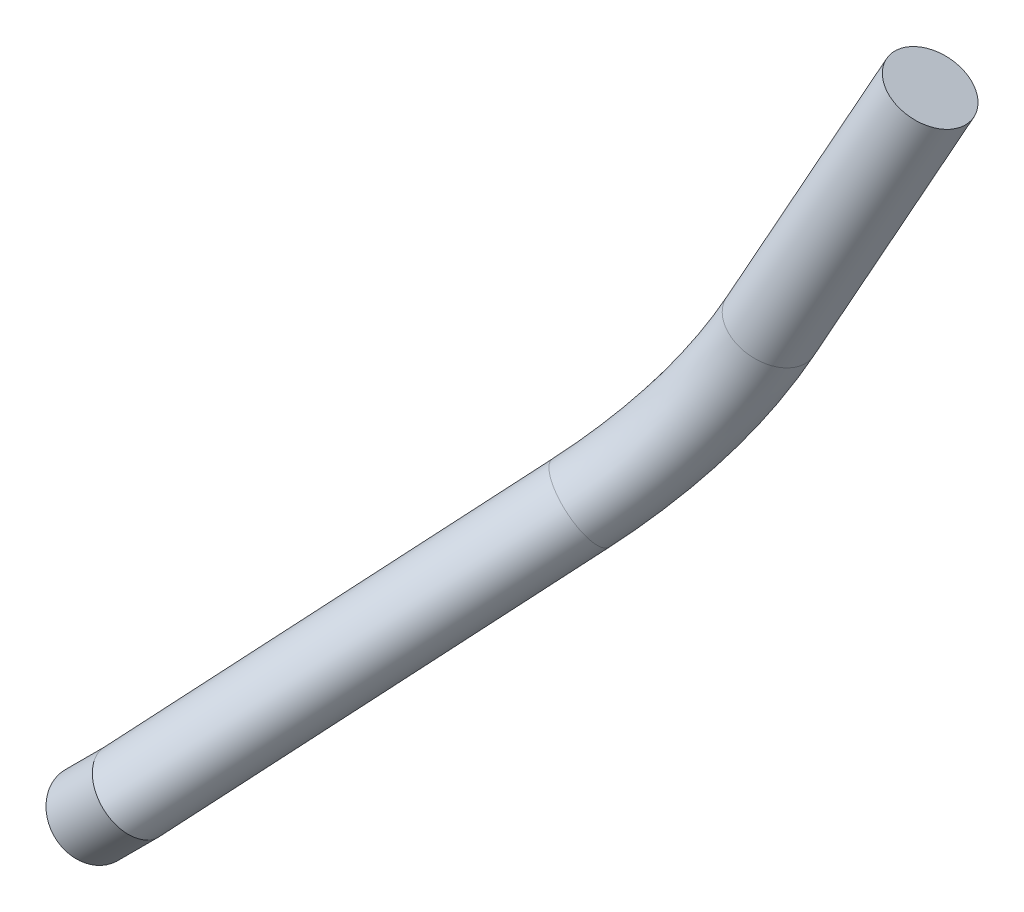
SolidWorks part; units mm, degrees
material "Custom Plastic"
ref_plane "X-Y Datum" through (0, 0, 0) normal (0, 0, 1) x (1, 0, 0)
ref_plane "X-Z Datum" through (0, 0, 0) normal (0, 1, 0) x (1, 0, 0)
ref_plane "Y-Z Datum" through (0, 0, 0) normal (1, 0, 0) x (0, 0, -1)
sketch3d "3DSketch1"
  line L0 (238.7544, 134.2697, 168.7024) -> (253.6203, 165.14, 163.3218)
  line L1 (198.0851, 82.9911, 208.7608) -> (193.0109, 77.9169, 208.7608)
  line L2 (198.0851, 82.9911, 208.7608) -> (225.2152, 113.3685, 179.1128)
  circle A0 centre (198.0851, 82.9911, 208.7608) radius 2.5146 construction
  arc A1 (253.6579, 165.1264, 159.3218) -> (253.6579, 165.1264, 167.3218) centre (253.6579, 165.1264, 163.3218) ccw construction
  arc A2 (253.6203, 165.14, 168.0218) -> (253.6203, 165.14, 158.6218) centre (253.6203, 165.14, 163.3218) ccw construction
  arc A3 (225.2152, 113.3685, 179.1128) -> (238.7544, 134.2697, 168.7024) centre (221.8528, 150.2787, 213.8543) ccw
  point P0 (198.0851, 82.9911, 208.7608)
  point P1 (253.6579, 165.1264, 163.3218)
  point P4 (199.8733, 84.7591, 208.7608)
  point P9 (252.2924, 161.3666, 163.3218)
  point P17 (252.0158, 160.7224, 163.3218)
  point P18 (232.7542, 121.8098, 170.8742)
  point P19 (264.5246, 133.5478, 235.7596)
  dimension "D1" = 50.8
sweep "Sweep1" add path "3DSketch1" circular profile diameter 9.398 parameters "D3"=9.398
